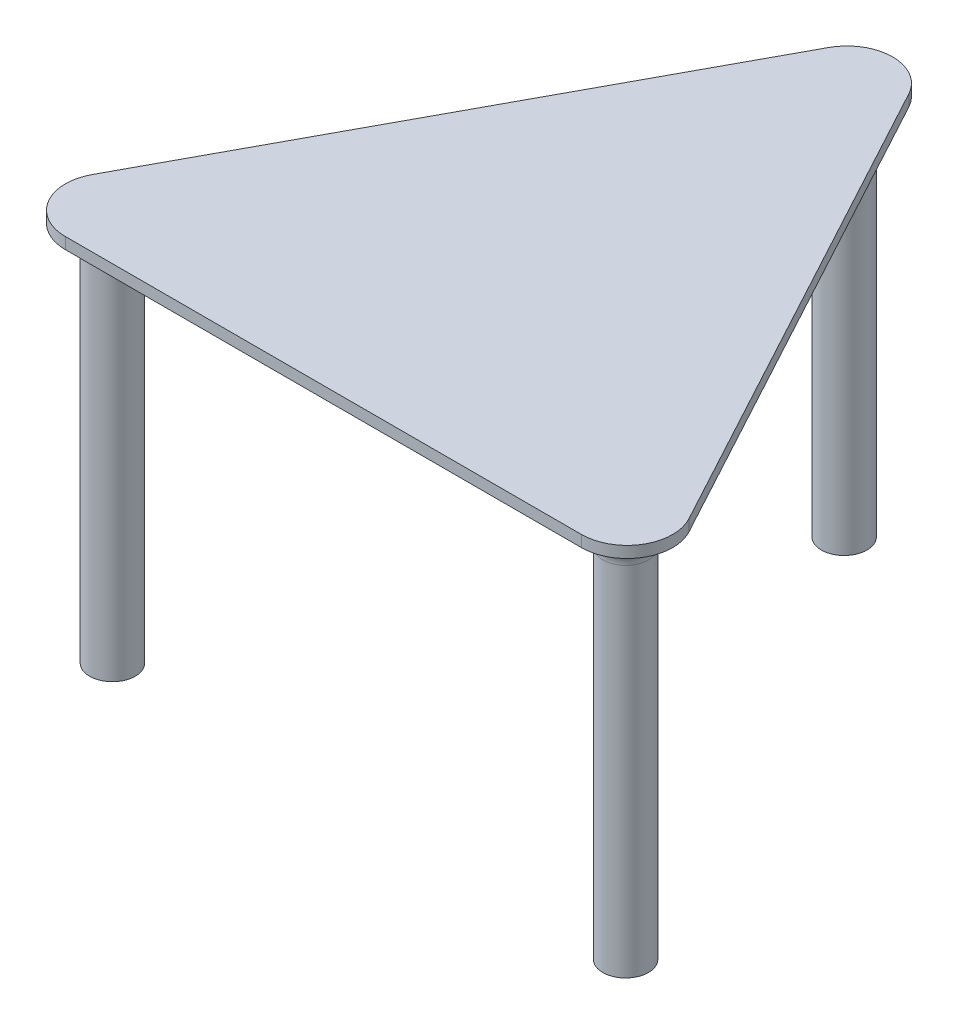
SolidWorks part; units mm, degrees
ref_plane "Front Plane" through (0, 0, 0) normal (0, 0, 1) x (1, 0, 0)
ref_plane "Top Plane" through (0, 0, 0) normal (0, 1, 0) x (1, 0, 0)
ref_plane "Right Plane" through (0, 0, 0) normal (1, 0, 0) x (0, 0, -1)
sketch "Sketch1" plane through (0, 0, 0) normal (0, 1, 0) x (1, 0, 0)
  line L0 (-45.1615, 35.4007) -> (-72.3152, -14.8954)
  line L1 (-68.0915, -21.9757) -> (-13.784, -21.9757)
  line L2 (-9.5602, -14.8954) -> (-36.714, 35.4007)
  circle A0 centre (-13.9377, -17.1757) radius 1
  circle A1 centre (-67.9377, -17.1757) radius 1
  circle A2 centre (-40.9377, 32.8243) radius 1
  circle A3 centre (-13.9377, -17.1757) radius 2.4
  circle A4 centre (-67.9377, -17.1757) radius 2.4
  circle A5 centre (-40.9377, 32.8243) radius 2.4
  arc A6 (-36.714, 35.4007) -> (-45.1615, 35.4007) centre (-40.9377, 33.1204) ccw
  arc A7 (-68.0915, -21.9757) -> (-72.3152, -14.8954) centre (-68.0915, -17.1757) cw
  arc A8 (-13.784, -21.9757) -> (-9.5602, -14.8954) centre (-13.784, -17.1757) ccw
  point P8 (-40.9377, -21.9757)
  point P18 (-40.9377, 43.2243)
  point P21 (-76.1377, -21.9757)
  point P24 (-5.7377, -21.9757)
  dimension "D1" = 2
  dimension "D2" = 4.8
  dimension "D3" = 2
  dimension "D4" = 4.8
  dimension "D5" = 2
  dimension "D6" = 4.8
  dimension "D13" = 4.8
  dimension "D14" = 4.8
  dimension "D15" = 4.8
  dimension "D7" = 50
  dimension "D8" = 27
  dimension "D9" = 27
  dimension "D10" = 70.4
  dimension "D11" = 65.2
  dimension "D12" = 10.4
extrude "Boss-Extrude1" add sketch "Sketch1" along normal blind 1.2 contours L1 A8 L2 A6 L0 A7 A3 A4 A5 | A5 A2 | A2 | A3 A0 | A0 | A4 A1 | A1 region at (-40.9377, 0, 0.2882) region at (-13.9377, 0, 17.1757) region at (-67.9377, 0, 17.1757) region at (-40.9377, 0, -32.8243) region at (-16.2698, 0, 17.1757) region at (-70.2698, 0, 17.1757) region at (-43.2698, 0, -32.8243)
extrude "Boss-Extrude2" add sketch "Sketch1<3>" against normal blind 40 contours A5 A2 | A4 A1 | A3 A0 region at (-16.2698, 0, 17.1757) region at (-70.2698, 0, 17.1757) region at (-43.2698, 0, -32.8243)
sketch "Sketch1<3>" plane through (0, 0, 0) normal (0, 1, 0) x (1, 0, 0) same geometry as "Sketch1"
sketch "Sketch2" plane through (0, 0, 0) normal (0, -1, 0) x (1, 0, 0)
  line L0 (-17.6019, 0) -> (-64.2735, 0) construction
  line L1 (-9.5602, 14.8954) -> (-36.714, -35.4007) construction
  line L2 (-45.1615, -35.4007) -> (-72.3152, 14.8954) construction
  text T0 "GPS\r\nthis side down"
extrude "Boss-Extrude3" [suppressed] add sketch "Sketch2" along normal blind 1
fillet "Fillet1" radius 2.4 3 edges at (-67.9377, 0, 19.5757) (-13.9377, 0, 19.5757) (-40.9377, 0, -30.4243)
